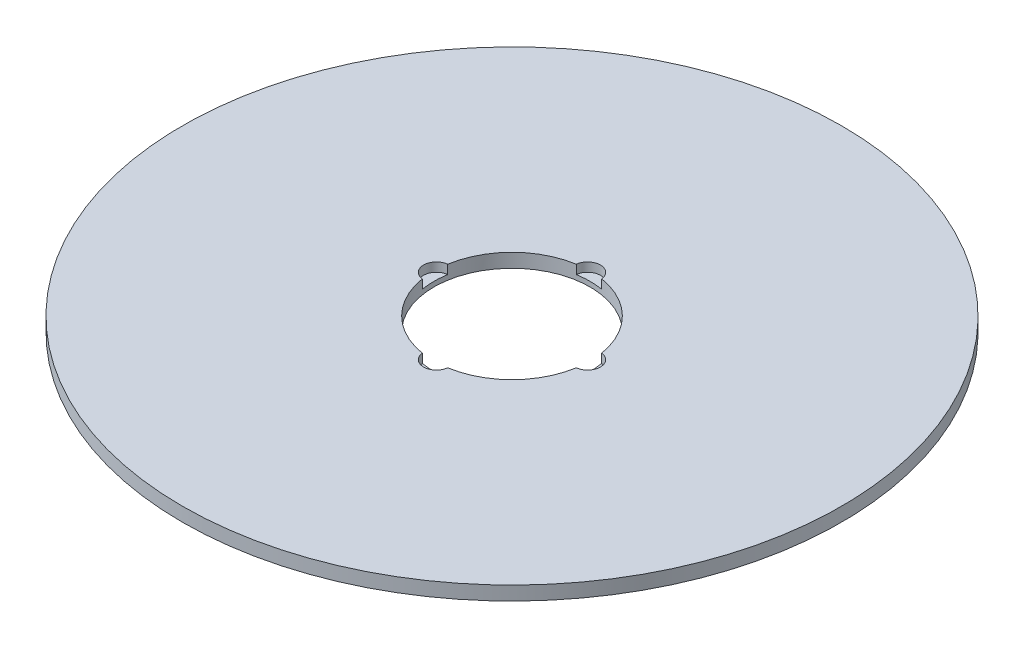
SolidWorks part; units mm, degrees
ref_plane "Front Plane" through (0, 0, 0) normal (0, 0, 1) x (1, 0, 0)
ref_plane "Top Plane" through (0, 0, 0) normal (0, 1, 0) x (1, 0, 0)
ref_plane "Right Plane" through (0, 0, 0) normal (1, 0, 0) x (0, 0, -1)
sketch "Sketch1" plane through (0, 0, 0) normal (0, 1, 0) x (1, 0, 0)
  circle A0 centre (0, 0) radius 95
  dimension "FLANGE_OD" = 190
extrude "Boss-Extrude1" add sketch "Sketch1" along normal blind 4
sketch "Sketch2" plane through (0, 0, 0) normal (0, 1, 0) x (1, 0, 0)
  circle A0 centre (0, 0) radius 22.5
  dimension "BORE_D" = 45
extrude "Cut-Extrude1" cut sketch "Sketch2" along normal through all
sketch "Sketch3" plane through (0, 4, 0) normal (0, 1, 0) x (1, 0, 0)
  circle A0 centre (0, 0) radius 21.7918 construction
  circle A1 centre (-21.7918, 0) radius 3.6897
  dimension "BOLT_D" = 7.3794
  dimension "BOLT_PCD" = 43.5837
extrude "Cut-Extrude2" cut sketch "Sketch3" against normal blind 2.5862
pattern_circular "CirPattern1" count 4 over 360 about axis through (0, 0, 0) along (0, 1, 0) of "Cut-Extrude2"
